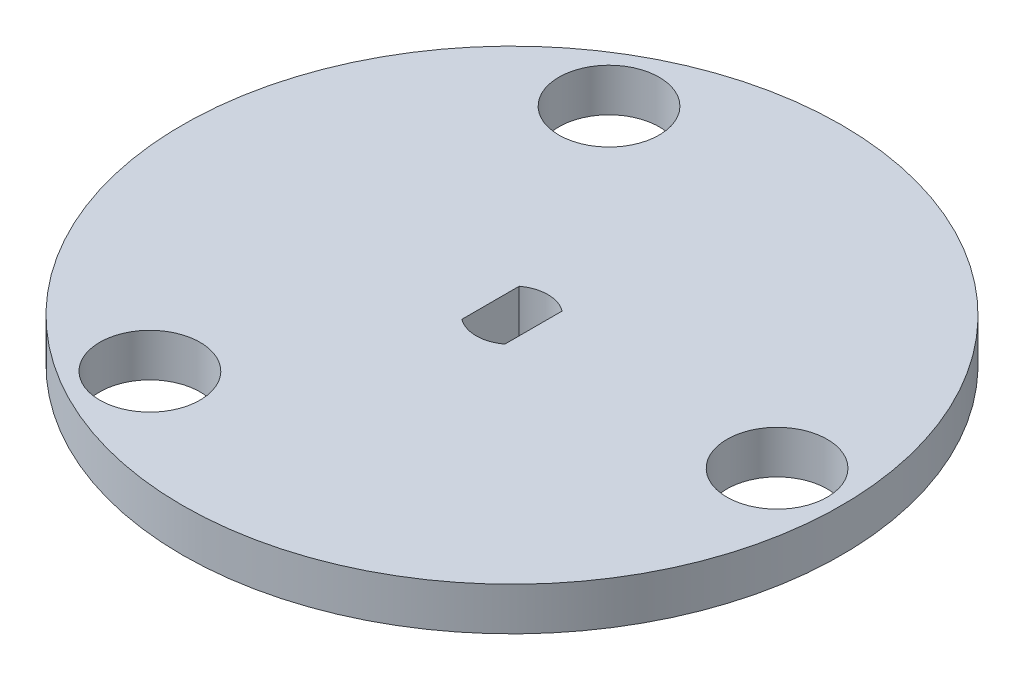
SolidWorks part; units mm, degrees
ref_plane "Alzado" through (0, 0, 0) normal (0, 0, 1) x (1, 0, 0)
ref_plane "Planta" through (0, 0, 0) normal (0, 1, 0) x (1, 0, 0)
ref_plane "Vista lateral" through (0, 0, 0) normal (1, 0, 0) x (0, 0, -1)
sketch "Croquis1" plane through (0, 0, 0) normal (0, 1, 0) x (1, 0, 0)
  line L0 (1.5, 0) -> (-1.5, 0)
  line L1 (-1.5, 0) -> (-1.5, 2)
  line L2 (-1.5, 0) -> (-1.5, -2)
  line L3 (0, 0) -> (-9.25, 16.0215) construction
  line L4 (1.5, 0) -> (1.5, -2)
  line L5 (1.5, 0) -> (1.5, 2)
  line L6 (0, 0) -> (-9.25, -16.0215)
  line L33 (0, 0) -> (18.5, 0) construction
  arc A0 (-1.5, -2) -> (1.5, -2) centre (0, 0) ccw
  circle A1 centre (0, 0) radius 3 construction
  circle A2 centre (0, 0) radius 23
  circle A3 centre (18.5, 0) radius 3.5
  arc A4 (1.5, 2) -> (-1.5, 2) centre (0, 0) ccw
  circle A5 centre (-9.25, 16.0215) radius 3.5
  circle A6 centre (-9.25, -16.0215) radius 3.5
  point P27 (0, 0)
  dimension "D2" = 1.5
  dimension "D7" = 120
  dimension "D12" = 7
  dimension "D3" = 5
  dimension "D6" = 7
  dimension "D9" = 7
  dimension "D4" = 120
  dimension "D5" = 18.5
  dimension "D8" = 18.5
  dimension "D13" = 18.5
extrude "Saliente-Extruir1" add sketch "Croquis1" along normal blind 3 contours A3 A1 L4 region at (-22.3495, 0, 0)
